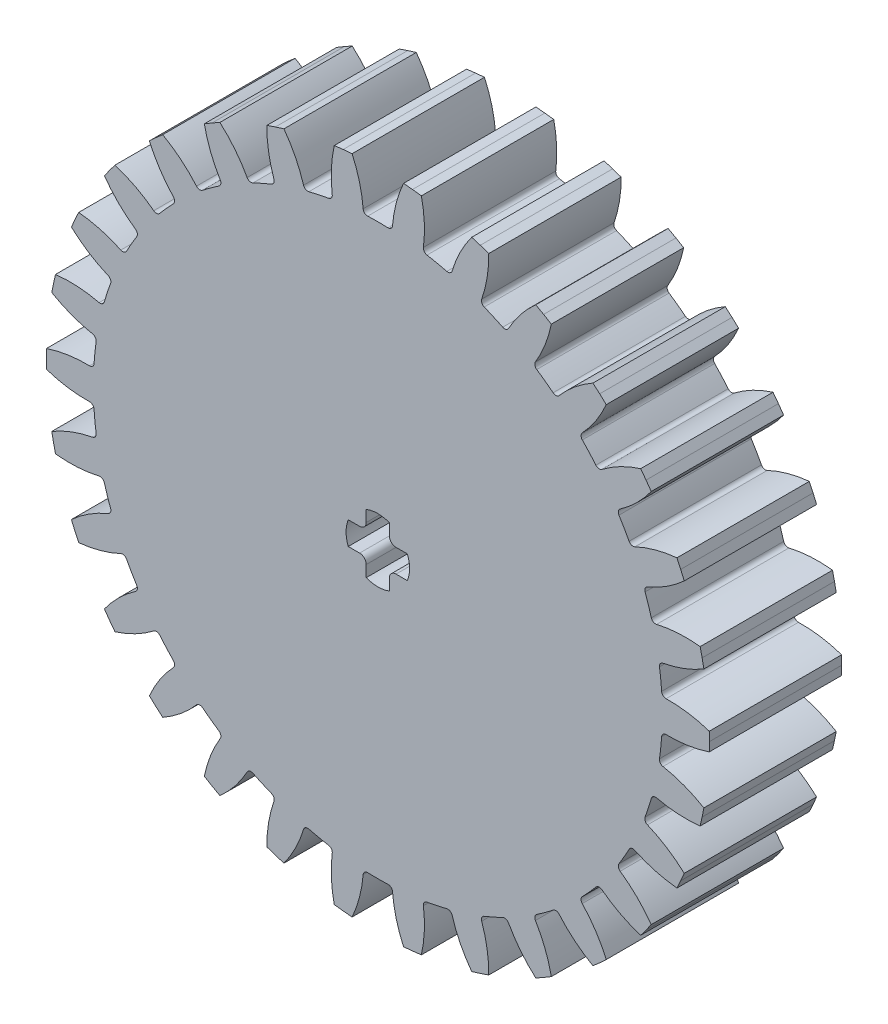
SolidWorks part; units mm, degrees
ref_plane "Front Plane" through (0, 0, 0) normal (0, 0, 1) x (1, 0, 0)
ref_plane "Top Plane" through (0, 0, 0) normal (0, 1, 0) x (1, 0, 0)
ref_plane "Right Plane" through (0, 0, 0) normal (1, 0, 0) x (0, 0, -1)
sketch "Sketch1" plane through (0, 0, 0) normal (0, 0, 1) x (1, 0, 0)
  line L0 (0, 0) -> (74.4139, 0) construction
  line L1 (0, 0) -> (21.3748, 2.2466) construction
  line L2 (0, 0) -> (74.4139, 4.0301) construction
  line L3 (0, 0) -> (74.4139, 2.0136) construction
  line L4 (25.0408, 0.6776) -> (25.05, 0)
  line L5 (0, 0) -> (21.3748, -2.2466) construction
  line L6 (0, 0) -> (21.3748, 2.2466)
  line L7 (0, 0) -> (21.3748, -2.2466) construction
  line L8 (0, 0) -> (21.3748, -2.2466)
  line L9 (25.0408, -0.6776) -> (25.05, 0)
  circle A0 centre (0, 0) radius 25.05 construction
  circle A1 centre (0, 0) radius 23.3875 construction
  circle A2 centre (0, 0) radius 21.4925 construction
  arc A3 (21.461, 1.1623) -> (25.0408, 0.6776) centre (21.9818, -8.4533) cw
  arc A4 (21.461, 1.1623) -> (21.3748, 2.2466) centre (0, 0) ccw
  arc A5 (21.461, -1.1623) -> (21.3748, -2.2466) centre (0, 0) cw
  arc A6 (21.461, -1.1623) -> (25.0408, -0.6776) centre (21.9818, 8.4533) ccw
  dimension "D1" = 50.1
  dimension "D2" = 1.6625
  dimension "D7" = 1.895
  dimension "D4" = 6
  dimension "D5" = 3.1
  dimension "D6" = 1.55
extrude "Boss-Extrude1" add sketch "Sketch1" along normal blind 10
fillet "Fillet1" radius 0.3325 2 edges at (21.461, 1.1623, 5) (21.461, -1.1623, 5)
pattern_circular "CirPattern1" count 30 over 360 about axis through (0, 0, 10) along (0, 0, -1) of "Boss-Extrude1", "Fillet1"
sketch "Sketch2" plane through (0, 0, 0) normal (0, 0, -1) x (-1, 0, 0)
  line L0 (0.875, 2.2348) -> (0.875, 1.375)
  line L1 (1.375, 0.875) -> (2.2348, 0.875)
  line L2 (2.4, 0) -> (-2.4, 0) construction
  line L3 (0, 2.4) -> (0, -2.4) construction
  line L4 (1.375, -0.875) -> (2.2348, -0.875)
  line L5 (0.875, -2.2348) -> (0.875, -1.375)
  line L6 (-0.875, -2.2348) -> (-0.875, -1.375)
  line L7 (-1.375, -0.875) -> (-2.2348, -0.875)
  line L8 (-1.375, 0.875) -> (-2.2348, 0.875)
  line L9 (-0.875, 2.2348) -> (-0.875, 1.375)
  arc A0 (-2.2348, -0.875) -> (-2.2348, 0.875) centre (0, 0) cw
  circle A1 centre (0, 0) radius 2.4 construction
  circle A2 centre (0, 0) radius 1.2374 construction
  arc A3 (-0.875, 2.2348) -> (0.875, 2.2348) centre (0, 0) cw
  arc A4 (-1.375, -0.875) -> (-0.875, -1.375) centre (-1.375, -1.375) cw
  arc A5 (0.875, -2.2348) -> (-0.875, -2.2348) centre (0, 0) cw
  arc A6 (2.2348, 0.875) -> (2.2348, -0.875) centre (0, 0) cw
  arc A7 (1.375, -0.875) -> (0.875, -1.375) centre (1.375, -1.375) ccw
  arc A8 (1.375, 0.875) -> (0.875, 1.375) centre (1.375, 1.375) cw
  arc A9 (-1.375, 0.875) -> (-0.875, 1.375) centre (-1.375, 1.375) ccw
  dimension "D1" = 4.8
  dimension "D2" = 0.5
  dimension "D5" = 2.4749
  dimension "D3" = 1.75
  dimension "D4" = 1.75
extrude "Cut-Extrude1" cut sketch "Sketch2" against normal up to next
